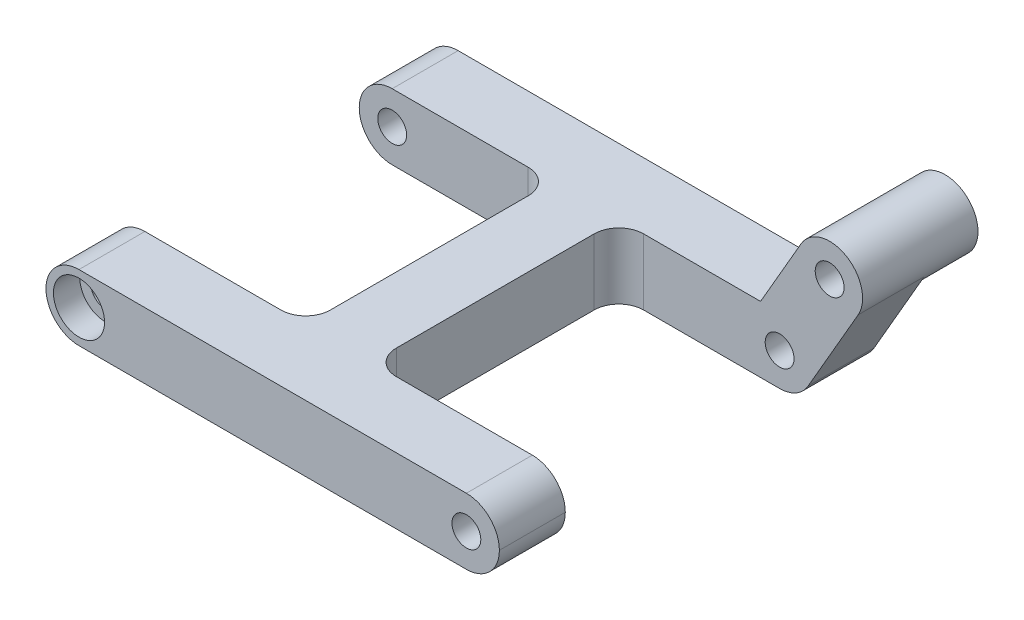
SolidWorks part; units mm, degrees
ref_plane "Alzado" through (0, 0, 0) normal (0, 0, 1) x (1, 0, 0)
ref_plane "Planta" through (0, 0, 0) normal (0, 1, 0) x (1, 0, 0)
ref_plane "Vista lateral" through (0, 0, 0) normal (1, 0, 0) x (0, 0, -1)
sketch "Croquis2" plane through (0, 0, 0) normal (0, 1, 0) x (1, 0, 0)
  line L5 (27.5, -23) -> (27.5, -15)
  line L6 (27.5, -15) -> (4, -15)
  line L7 (4, -15) -> (4, 15)
  line L8 (4, 15) -> (27.5, 15)
  line L9 (27.5, 15) -> (27.5, 23)
  line L24 (-35, 0) -> (35, 0) construction
  line L35 (27.5, 23) -> (-27.5, 23)
  line L36 (27.5, -23) -> (-27.5, -23)
  line L37 (-27.5, -23) -> (-27.5, -15)
  line L38 (-27.5, -15) -> (-4, -15)
  line L39 (-4, -15) -> (-4, 15)
  line L40 (-4, 15) -> (-27.5, 15)
  line L41 (-27.5, 15) -> (-27.5, 23)
  line L42 (0, 23) -> (0, -23) construction
  dimension "D1" = 55
  dimension "D2" = 55
  dimension "D3" = 4
  dimension "D4" = 4
  dimension "D5" = 8
  dimension "D6" = 8
  dimension "D7" = 23.5
  dimension "D8" = 30
  dimension "D9" = 30
extrude "Saliente-Extruir1" add sketch "Croquis2" along normal mid plane 8
sketch "Croquis3" plane through (0, 0, 23) normal (0, 0, 1) x (1, 0, 0)
  line L2 (-27.5, 4) -> (-27.5, -4) construction
  line L5 (27.5, 4) -> (27.5, -4) construction
  line L6 (-27.5, -4) -> (27.5, -4) construction
  circle A0 centre (23.5, 0) radius 1.75
  circle A1 centre (-23.5, 0) radius 1.75
  dimension "D1" = 3.5
  dimension "D2" = 3.5
  dimension "D3" = 4
  dimension "D6" = 4
  dimension "D4" = 4
  dimension "D5" = 4
extrude "Cortar-Extruir1" cut sketch "Croquis3" against normal through all
fillet "Redondeo8" radius 4 8 edges at (27.5, -4, -19) (27.5, 4, -19) (27.5, -4, 19) (27.5, 4, 19) (-27.5, -4, -19) (-27.5, 4, -19) (-27.5, -4, 19) (-27.5, 4, 19)
fillet "Redondeo9" radius 3 4 edges at (4, 0, 15) (4, 0, -15) (-4, 0, 15) (-4, 0, -15)
sketch "Croquis5" plane through (0, 0, -23) normal (0, 0, -1) x (-1, 0, 0)
  line L0 (-26.1037, 12.5098) -> (-20.0359, 2)
  line L1 (-33.0319, 8.5098) -> (-26.9641, -2)
  line L2 (-29.5678, 10.5098) -> (-23.5, 0) construction
  circle A0 centre (-23.5, 0) radius 1.75
  circle A1 centre (-29.5678, 10.5098) radius 1.75
  arc A2 (-26.1037, 12.5098) -> (-33.0319, 8.5098) centre (-29.5678, 10.5098) ccw
  arc A3 (-26.9641, -2) -> (-20.0359, 2) centre (-23.5, 0) ccw
  dimension "D1" = 8
  dimension "D2" = 8
  dimension "D3" = 3.5
  dimension "D4" = 3.5
  dimension "D5" = 120
extrude "Saliente-Extruir3" add sketch "Croquis5" against normal blind 8
sketch "Croquis4" plane through (0, 0, -23) normal (0, 0, 1) x (1, 0, 0)
  circle A0 centre (29.5678, 10.5098) radius 4
  circle A2 centre (29.5678, 10.5098) radius 1.75
  dimension "D1" = 8
extrude "Saliente-Extruir2" add sketch "Croquis4" against normal blind 6
sketch "Croquis6" plane through (0, 0, 23) normal (0, 0, 1) x (1, 0, 0)
  circle A0 centre (-23.5, 0) radius 3.1
  dimension "D1" = 6.2
extrude "Cortar-Extruir2" cut sketch "Croquis6" against normal blind 3.2
